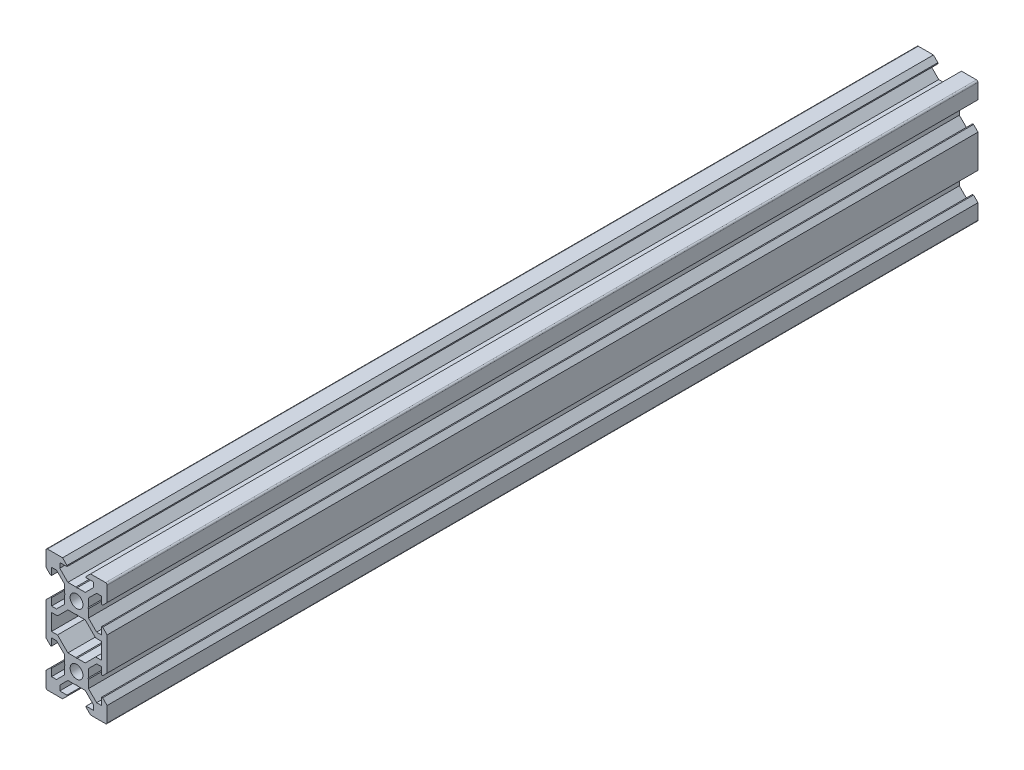
SolidWorks part; units mm, degrees
ref_plane "Plan de face" through (0, 0, 0) normal (0, 0, 1) x (1, 0, 0)
ref_plane "Plan de dessus" through (0, 0, 0) normal (0, 1, 0) x (1, 0, 0)
ref_plane "Plan de droite" through (0, 0, 0) normal (1, 0, 0) x (0, 0, -1)
ref_axis "Axe" through (0, 0, -13.782) along (0, 0, 1)
sketch "Esquisse1" plane through (0, 0, 0) normal (0, 0, 1) x (1, 0, 0)
  line L0 (0, 22.8977) -> (0, -22.8977) construction
  line L1 (-33.6074, 0) -> (33.6074, 0) construction
  line L2 (0, 0) -> (-22.2114, 22.2114) construction
  line L3 (-9.5, 10) -> (-4.58, 10)
  line L4 (-4.58, 10) -> (-3.125, 8.545)
  line L5 (-3.125, 8.545) -> (-3.125, 8.2)
  line L6 (-3.125, 8.2) -> (-5.5, 8.2)
  line L7 (-2.8393, 3.9) -> (-5.5, 6.5607)
  line L8 (-2.8393, 3.9) -> (-0.21, 3.9)
  line L9 (-5.5, 6.5607) -> (-5.5, 8.2)
  line L10 (0, 3.69) -> (0, 2.1)
  line L11 (-3.9, 2.8393) -> (-6.5607, 5.5)
  line L12 (-8.545, 3.125) -> (-8.2, 3.125)
  line L13 (-8.2, 3.125) -> (-8.2, 5.5)
  line L14 (-6.5607, 5.5) -> (-8.2, 5.5)
  line L15 (-10, 4.58) -> (-8.545, 3.125)
  line L16 (-10, 9.5) -> (-10, 4.58)
  line L17 (-0.21, 3.9) -> (0, 3.69)
  line L18 (-3.9, 2.8393) -> (-3.9, 0.21)
  line L20 (-3.9, 0.21) -> (-3.69, 0)
  line L21 (-0.21, -3.9) -> (0, -3.69)
  line L22 (0, -3.69) -> (0, -2.1)
  line L23 (-6.5607, -5.5) -> (-8.2, -5.5)
  line L24 (-2.8393, -3.9) -> (-0.21, -3.9)
  line L25 (-8.545, -3.125) -> (-8.2, -3.125)
  line L26 (-10, -4.58) -> (-8.545, -3.125)
  line L27 (-8.2, -3.125) -> (-8.2, -5.5)
  line L28 (-2.8393, -3.9) -> (-6.2393, -7.3)
  line L29 (-3.9, -2.8393) -> (-6.5607, -5.5)
  line L30 (-3.9, -2.8393) -> (-3.9, -0.21)
  line L31 (-3.9, -0.21) -> (-3.69, 0)
  line L32 (-6.2393, -7.3) -> (-8.2, -7.3)
  line L33 (-8.2, -7.3) -> (-8.2, -10)
  line L34 (-8.2, -10) -> (-10, -10)
  line L35 (-10, -10) -> (-10, -4.58)
  arc A0 (0, -2.1) -> (0, 2.1) centre (0, 0) cw
  arc A1 (-9.5, 10) -> (-10, 9.5) centre (-9.5, 9.5) ccw
  point P4 (0, 0)
  point P7 (0, 0)
  point P30 (-10, 10)
  dimension "D5" = 11
  dimension "D2" = 2.1
  dimension "D3" = 6.25
  dimension "D10" = 0.5
  dimension "D4" = 9.16
  dimension "D6" = 1.5
  dimension "D7" = 1.8
  dimension "D8" = 4.3
  dimension "D9" = 20
  dimension "D11" = 0.42
  dimension "D12" = 10
  dimension "D13" = 1.8
extrude "Boss.-Extru.1" add sketch "Esquisse1" along normal blind 285
sketch "Esquisse3" plane through (0, 0, 285) normal (0, 0, 1) x (1, 0, 0)
  line L0 (0, 0) -> (-9.8536, 9.8536) construction
  line L1 (-8.2, 8.2) -> (-8.2, 6.57)
  line L2 (-8.2, 6.57) -> (-7.54, 6.57)
  line L3 (-7.54, 6.57) -> (-6.57, 7.54)
  line L4 (-8.2, 3.125) -> (-8.2, 5.5) construction
  line L5 (-6.57, 8.2) -> (-6.57, 7.54)
  line L6 (-8.2, 8.2) -> (-6.57, 8.2)
  line L7 (-5.5, 6.5607) -> (-5.5, 8.2) construction
  arc A0 (-9.5, 10) -> (-10, 9.5) centre (-9.5, 9.5) ccw construction
  point P13 (-7.055, 7.055)
  point P14 (-6.57, 7.87)
  dimension "D1" = 1.07
extrude "Enlèv. mat.-Extru.1" [suppressed] cut sketch "Esquisse3" against normal through all
mirror "Symétrie1" about plane through (0, 3.69, 285) normal (-1, 0, 0) of "Enlèv. mat.-Extru.1", "Boss.-Extru.1"
mirror "Symétrie6" about plane through (-8.2, -10, 285) normal (0, 1, 0) of "Symétrie1", "Boss.-Extru.1"
